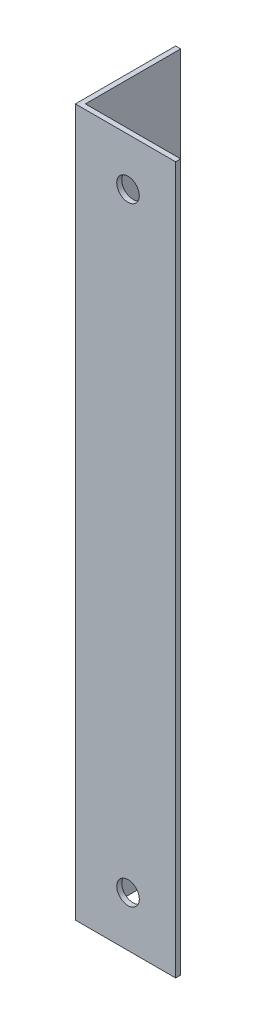
SolidWorks part; units mm, degrees
material "1060 Сплав"
ref_plane "Спереди" through (0, 0, 0) normal (0, 0, 1) x (1, 0, 0)
ref_plane "Сверху" through (0, 0, 0) normal (0, 1, 0) x (1, 0, 0)
ref_plane "Справа" through (0, 0, 0) normal (1, 0, 0) x (0, 0, -1)
sketch "Эскиз1" plane through (0, 0, 0) normal (0, 1, 0) x (1, 0, 0)
  line L0 (0, 0) -> (0, 20)
  line L1 (0, 20) -> (1, 20)
  line L2 (1, 20) -> (1, 1)
  line L3 (1, 1) -> (20, 1)
  line L4 (20, 1) -> (20, 0)
  line L5 (20, 0) -> (0, 0)
  dimension "D1" = 1
  dimension "D2" = 20
extrude "Бобышка-Вытянуть1" add sketch "Эскиз1" along normal blind 141
sketch "Эскиз2" plane through (0, 0, -1) normal (0, 0, -1) x (-1, 0, 0)
  line L0 (-10.5, 0) -> (-10.5, 141) construction
  line L1 (-20, 0) -> (-1, 0) construction
  line L2 (-20, 141) -> (-1, 141) construction
  circle A0 centre (-10.5, 10) radius 2.25
  circle A1 centre (-10.5, 131.5) radius 2.25
  dimension "D1" = 4.5
  dimension "D2" = 4.5
  dimension "D3" = 10
  dimension "D4" = 9.5
extrude "Вырез-Вытянуть1" cut sketch "Эскиз2" against normal through all
